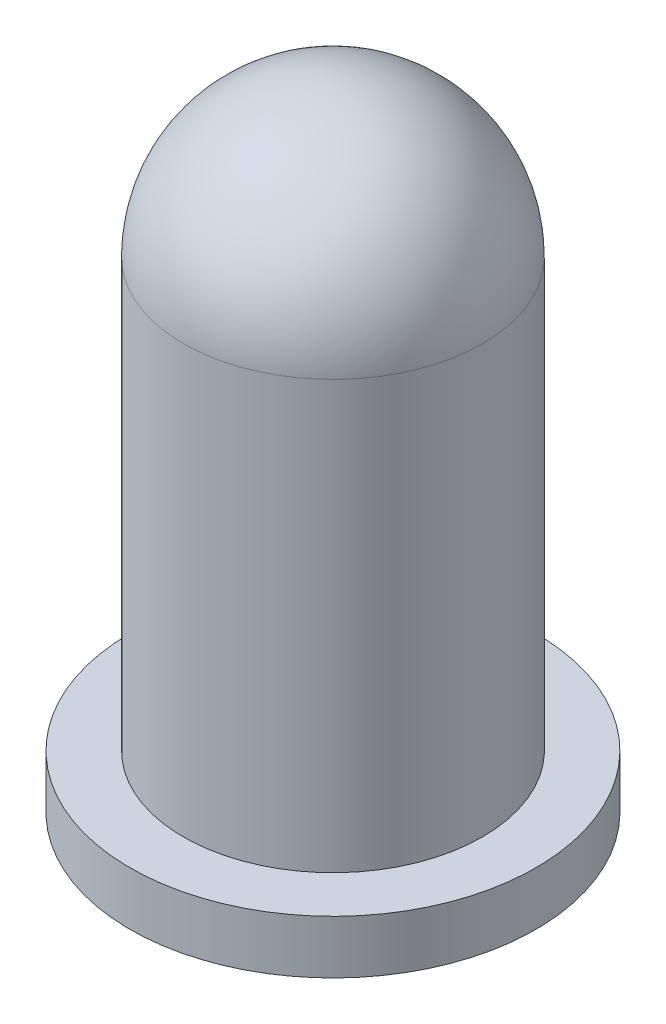
SolidWorks part; units mm, degrees
material "有机玻璃 (TM) GS 丙烯酸铸钣"
ref_plane "前视基准面" through (0, 0, 0) normal (0, 0, 1) x (1, 0, 0)
ref_plane "上视基准面" through (0, 0, 0) normal (0, 1, 0) x (1, 0, 0)
ref_plane "右视基准面" through (0, 0, 0) normal (1, 0, 0) x (0, 0, -1)
sketch "Sketch1" plane through (0, 0, 0) normal (0, 0, 1) x (1, 0, 0)
  line L0 (1.4, 0.5) -> (1.4, 4.5)
  line L1 (0, 0) -> (1.4, 0)
  line L2 (1.4, 0) -> (1.9, 0)
  line L3 (0, 5.9) -> (0, 0)
  line L4 (1.4, 0.5) -> (1.9, 0.5)
  line L5 (1.9, 0) -> (1.9, 0.5)
  arc A0 (1.4, 4.5) -> (0, 5.9) centre (0, 4.5) ccw
  dimension "D3" = 0.5
  dimension "D1" = 4.5
  dimension "D2" = 1.4
  dimension "D4" = 0.5
ref_axis "Axis1" through (0, 0, 0) along (0, 1, 0)
revolve "Revolve2" add sketch "Sketch1" angle 360 about L3
